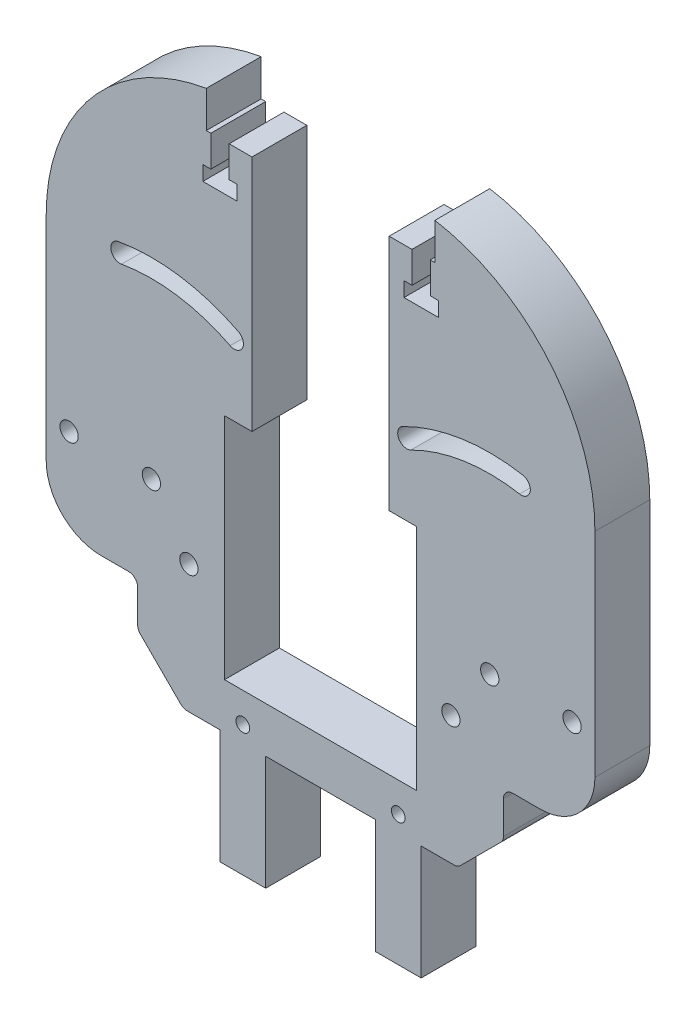
SolidWorks part; units mm, degrees
material "Maple"
ref_plane "Front Plane" through (0, 0, 0) normal (0, 0, 1) x (1, 0, 0)
ref_plane "Top Plane" through (0, 0, 0) normal (0, 1, 0) x (1, 0, 0)
ref_plane "Right Plane" through (0, 0, 0) normal (1, 0, 0) x (0, 0, -1)
sketch "Sketch1" plane through (0, 0, 0) normal (0, 0, 1) x (1, 0, 0)
  line L0 (0, 0) -> (0, -98.0129) construction
  line L1 (-40, 60) -> (-25, 60)
  line L2 (-40, 60) -> (-40, -60)
  line L3 (-40, -60) -> (-22, -60)
  line L4 (40, 60) -> (40, -60)
  line L5 (-40, 60) -> (40, -60) construction
  line L6 (-40, -60) -> (40, 60) construction
  line L7 (21, 0) -> (21, -50)
  line L8 (0, 0) -> (0, 75) construction
  line L9 (-21, -50) -> (21, -50)
  line L10 (15, 0) -> (15, 52)
  line L11 (-15, 0) -> (-15, 52)
  line L12 (-15, 0) -> (-15, 85.1588) construction
  line L13 (0, 0) -> (0, 85.1588) construction
  line L14 (15, 0) -> (15, 85.1588) construction
  line L15 (25, 60) -> (40, 60)
  line L16 (-15, 0) -> (-21, 0)
  line L17 (15, 0) -> (21, 0)
  line L18 (-21, 0) -> (-21, -50)
  line L19 (-12, -60) -> (12, -60)
  line L21 (-15, 52) -> (-25, 52)
  line L22 (-25, 60) -> (-25, 52)
  line L23 (22, -60) -> (22, -85)
  line L24 (22, -85) -> (12, -85)
  line L25 (15, 52) -> (25, 52)
  line L26 (25, 60) -> (25, 52)
  line L27 (12, -60) -> (12, -85)
  line L28 (22, -60) -> (40, -60)
  line L29 (-12, -60) -> (-12, -85)
  line L30 (-12, -85) -> (-22, -85)
  line L31 (-22, -60) -> (-22, -85)
  point P0 (0, 0)
  dimension "D1" = 120
  dimension "D2" = 80
  dimension "D3" = 50
  dimension "D4" = 8
  dimension "D5" = 110
  dimension "D8" = 8
  dimension "D9" = 50
  dimension "D10" = 25
  dimension "D11" = 42
  dimension "D12" = 25
  dimension "D13" = 10
  dimension "D14" = 24
  dimension "D15" = 12
  dimension "D6" = 15
  dimension "D7" = 15
extrude "Boss-Extrude1" add sketch "Sketch1" along normal blind 12
sketch "Sketch2" plane through (0, 0, 0) normal (0, 0, -1) x (-1, 0, 0)
  line L1 (-21, 0) -> (-21, -50) construction
  line L2 (40, -60) -> (22, -60) construction
  line L3 (28.8, -32) -> (28.8, 8.3751) construction
  line L4 (22, -85) -> (12, -85) construction
  line L5 (-12, -85) -> (-22, -85) construction
  line L6 (21, -50) -> (21, 0) construction
  line L7 (-28.5, -12) -> (-28.5, -69.2337) construction
  line L9 (40, -60) -> (22, -60) construction
  circle A0 centre (-28.5, -32) radius 2
  circle A1 centre (17, -56.5) radius 1.5
  circle A2 centre (28.8, -32) radius 2
  circle A3 centre (-17, -56.5) radius 1.5
  point P21 (17, -85)
  point P24 (-17, -85)
  dimension "D1" = 4
  dimension "D6" = 3
  dimension "D2" = 7.5
  dimension "D3" = 57.3
  dimension "D4" = 28
  dimension "D5" = 28
  dimension "D7" = 3.5
extrude "Cut-Extrude1" cut sketch "Sketch2" against normal through all
ref_plane "Plane1" through (0, 0, 6) normal (0, 0, 1) x (1, 0, 0)
sketch "Sketch4" plane through (0, 0, 12) normal (0, 0, 1) x (1, 0, 0)
  line L1 (-40, 60) -> (-60, 60)
  line L2 (-40, 60) -> (-40, -40)
  line L3 (-40, -40) -> (-60, -40)
  line L4 (-60, 60) -> (-60, -40)
  line L5 (40, 60) -> (60, 60)
  line L6 (40, 60) -> (40, -40)
  line L7 (40, -40) -> (60, -40)
  line L8 (60, 60) -> (60, -40)
  dimension "D1" = 20
  dimension "D2" = 20
  dimension "D3" = 100
  dimension "D4" = 100
extrude "Boss-Extrude2" add sketch "Sketch4" against normal blind 12
fillet "Fillet3" radius 42 2 edges at (60, 60, 6) (-60, 60, 6)
fillet "Fillet4" radius 12 2 edges at (60, -40, 6) (-60, -40, 6)
sketch "Sketch7" plane through (0, 0, 0) normal (0, 0, 1) x (1, 0, 0)
  line L1 (-60, 18.5874) -> (-60, -28) construction
  line L2 (60, -28) -> (60, 18.5874) construction
  line L3 (22, -60) -> (40, -60) construction
  line L4 (-40, -60) -> (-22, -60) construction
  circle A0 centre (-55, -20) radius 2
  circle A1 centre (55, -20) radius 2
  circle A2 centre (-37, -20) radius 2
  circle A3 centre (37, -20) radius 2
  point P10 (-60, -4.7063)
  dimension "D3" = 5
  dimension "D4" = 5
  dimension "D5" = 4
  dimension "D6" = 4
  dimension "D7" = 4
  dimension "D1" = 40
  dimension "D2" = 40
  dimension "D8" = 18
  dimension "D9" = 18
extrude "Cut-Extrude3" cut sketch "Sketch7" along normal through all
chamfer "Chamfer1" distance 10 angle 45 2 edges at (-40, -60, 6) (40, -60, 6)
fillet "Fillet8" radius 2 6 edges at (-30, -60, 6) (-40, -50, 6) (30, -60, 6) (40, -50, 6)
sketch "Sketch8" plane through (0, 0, 0) normal (0, 0, -1) x (-1, 0, 0)
  line L0 (0, 0) -> (0, 75) construction
  line L1 (0, 0) -> (0, 75)
  circle A0 centre (-37, -20) radius 40 construction
  arc A1 (-18.8713, 15.656) -> (-43.8713, 19.4054) centre (-37, -20) ccw construction
  arc A2 (-17.9648, 17.4388) -> (-44.2148, 21.3757) centre (-37, -20) ccw
  arc A3 (-19.7777, 13.8732) -> (-43.5277, 17.4351) centre (-37, -20) ccw
  arc A4 (-19.7777, 13.8732) -> (-17.9648, 17.4388) centre (-18.8713, 15.656) ccw
  arc A5 (-44.2148, 21.3757) -> (-43.5277, 17.4351) centre (-43.8713, 19.4054) ccw
  arc A6 (18.8713, 15.656) -> (43.8713, 19.4054) centre (37, -20) cw construction
  arc A7 (17.9648, 17.4388) -> (44.2148, 21.3757) centre (37, -20) cw
  arc A8 (19.7777, 13.8732) -> (43.5277, 17.4351) centre (37, -20) cw
  arc A9 (19.7777, 13.8732) -> (17.9648, 17.4388) centre (18.8713, 15.656) cw
  arc A10 (44.2148, 21.3757) -> (43.5277, 17.4351) centre (43.8713, 19.4054) cw
  point P5 (-31.0673, 19.5576)
  point P15 (31.0673, 19.5576)
  dimension "D1" = 80
  dimension "D2" = 2
  dimension "D3" = 25
extrude "Cut-Extrude4" cut sketch "Sketch8" against normal through all contours A7 A10 A8 A9 | A2 A5 A3 A4
sketch "Sketch9" plane through (0, 0, 12) normal (0, 0, 1) x (1, 0, 0)
  line L0 (-15, 52) -> (-25, 52) construction
  line L1 (-24, 52) -> (-20, 52)
  line L2 (-24, 52) -> (-24, 45.2)
  line L3 (-22, 40.3094) -> (-22, 51.6327) construction
  line L4 (-20, 52) -> (-20, 45.2)
  line L5 (-25, 52) -> (-25, 60) construction
  line L6 (-20, 45.2) -> (-18.25, 45.2)
  line L7 (-25.75, 45.2) -> (-24, 45.2)
  line L8 (-25.75, 45.2) -> (-25.75, 42)
  line L9 (-25.75, 42) -> (-18.25, 42)
  line L10 (-18.25, 45.2) -> (-18.25, 42)
  dimension "D1" = 3
  dimension "D2" = 2
  dimension "D3" = 2
  dimension "D4" = 7.5
  dimension "D5" = 3.2
  dimension "D6" = 10
  dimension "D7" = 3.75
extrude "Cut-Extrude5" cut sketch "Sketch9" against normal through all
mirror "Mirror1" about plane through (0, 0, 0) normal (1, 0, 0) of "Cut-Extrude5"
